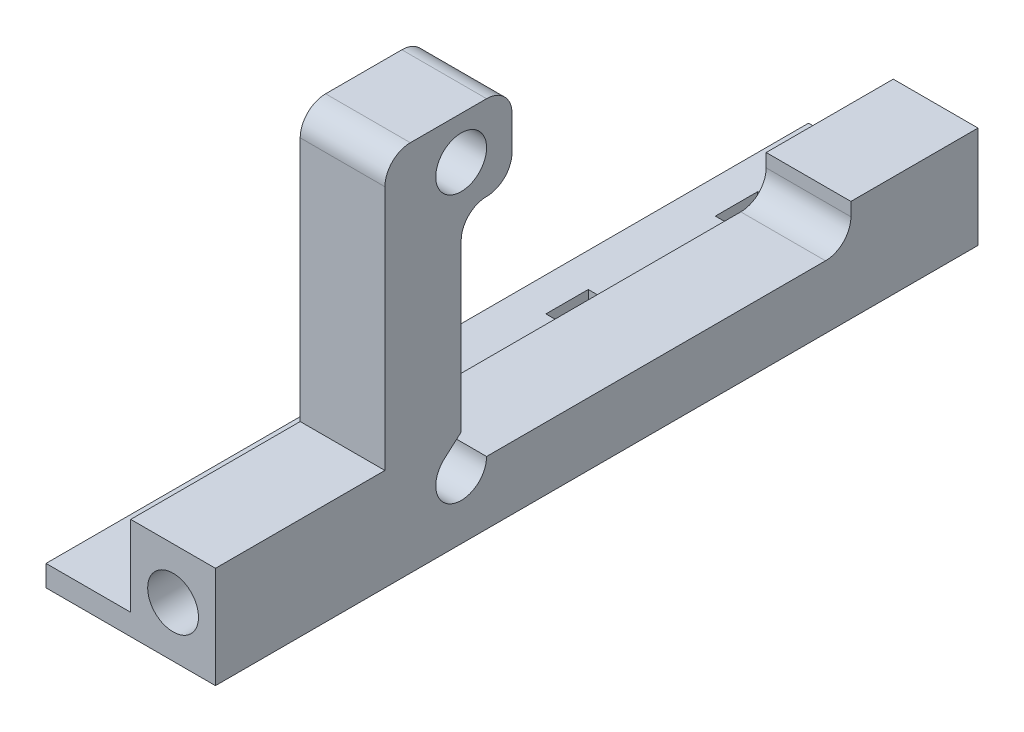
SolidWorks part; units mm, degrees
ref_plane "Plano frontal" through (0, 0, 0) normal (0, 0, 1) x (1, 0, 0)
ref_plane "Plano superior" through (0, 0, 0) normal (0, 1, 0) x (1, 0, 0)
ref_plane "Plano direito" through (0, 0, 0) normal (1, 0, 0) x (0, 0, -1)
sketch "Esboço1" plane through (0, 0, 0) normal (1, 0, 0) x (0, 0, -1)
  line L0 (0, 44) -> (0, 0)
  line L1 (0, 0) -> (70, 0)
  line L2 (70, 0) -> (70, 12)
  line L3 (70, 12) -> (15, 12)
  line L4 (15, 12) -> (15, 44)
  line L5 (15, 44) -> (0, 44)
  line L6 (15, 34) -> (9, 34)
  line L7 (9, 34) -> (9, 7.43)
  line L8 (9, 7.43) -> (55, 7.43)
  line L9 (55, 7.43) -> (55, 12)
  line L10 (0, 12) -> (-20, 12)
  line L11 (-20, 12) -> (-20, 0)
  line L12 (-20, 0) -> (0, 0)
  line L13 (9, 11.43) -> (7.0157, 9.68)
  circle A0 centre (9, 39) radius 3
  circle A1 centre (9, 7.43) radius 3
  dimension "D1" = 6
  dimension "D4" = 6
  dimension "D5" = 6
  dimension "D2" = 39
  dimension "D3" = 15
  dimension "D6" = 44
  dimension "D7" = 10
  dimension "D8" = 9
  dimension "D9" = 70
  dimension "D10" = 15
  dimension "D11" = 7.43
  dimension "D12" = 20
  dimension "D13" = 12
  dimension "D14" = 4
extrude "Ressalto-extrusão1" add sketch "Esboço1" along normal blind 10 contours L11 L12 L0 L10 | A1 L7 L6 L4 L5 L0 L1 L2 L3 L9 L8 A0 region at (0, 43.1732, -7.5) region at (0, 6, 10)
sketch "Esboço2" plane through (0, 0, -70) normal (0, 0, -1) x (-1, 0, 0)
  line L0 (-10, 0) -> (0, 0) construction
  line L1 (-5, 0) -> (-5, 6) construction
  circle A0 centre (-5, 6) radius 3
  dimension "D1" = 6
  dimension "D2" = 6
extrude "Corte-extrusão1" cut sketch "Esboço2" against normal blind 10
extrude "Corte-extrusão2" cut sketch "Esboço2<2>" along normal blind 10 from surface starting at face at (5, 6, 20)
sketch "Esboço2<2>" plane through (0, 0, -70) normal (0, 0, -1) x (-1, 0, 0) same geometry as "Esboço2"
fillet "Filete1" radius 3 5 edges at (5, 7.43, -55) (5, 44, 0) (5, 44, -15) (5, 34, -15) (5, 34, -9)
sketch "Esboço3" plane through (0, 0, 0) normal (-1, 0, 0) x (0, 0, 1)
  line L0 (20, 12) -> (20, 0) construction
  line L1 (-70, 0) -> (20, 0)
  line L2 (-70, 0) -> (-70, 2.5)
  line L3 (-70, 2.5) -> (20, 2.5)
  line L4 (20, 0) -> (20, 2.5)
  dimension "D1" = 2.5
extrude "Ressalto-extrusão2" add sketch "Esboço3" along normal blind 10
sketch "Esboço4" plane through (0, 2.5, 0) normal (0, 1, 0) x (1, 0, 0)
  line L0 (-10, -20) -> (-10, 70) construction
  line L1 (-6, 60) -> (-4, 60)
  line L2 (-6, 60) -> (-6, 55)
  line L3 (-6, 55) -> (-4, 55)
  line L4 (-4, 60) -> (-4, 55)
  line L5 (-10, 70) -> (0, 70) construction
  dimension "D1" = 5
  dimension "D2" = 2
  dimension "D3" = 4
  dimension "D4" = 10
extrude "Corte-extrusão3" cut sketch "Esboço4" against normal blind 10
pattern_linear "Padrão linear1" count 4 spacing 20 along (0, 0, 1) of "Corte-extrusão3"
